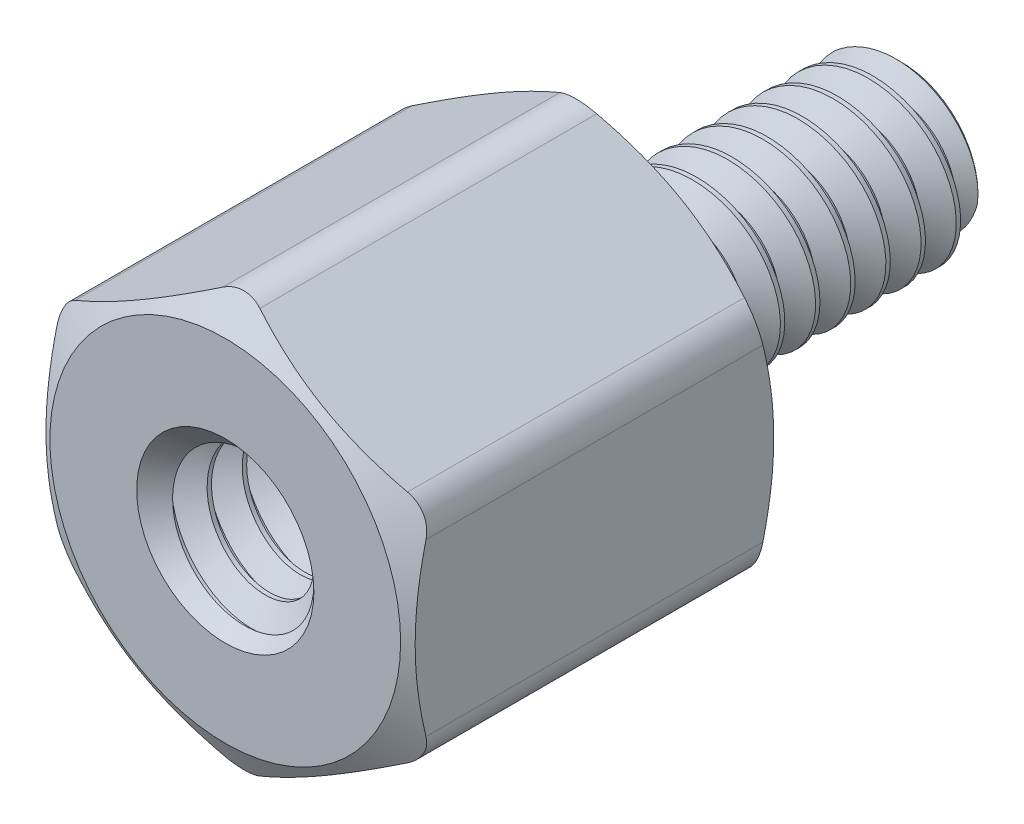
SolidWorks part; units mm, degrees
ref_plane "Front Plane" through (0, 0, 0) normal (0, 0, 1) x (1, 0, 0)
ref_plane "Top Plane" through (0, 0, 0) normal (0, 1, 0) x (1, 0, 0)
ref_plane "Right Plane" through (0, 0, 0) normal (1, 0, 0) x (0, 0, -1)
sketch "Sketch1" plane through (0, 0, 0) normal (0, 0, 1) x (1, 0, 0)
  line L1 (2.3813, 1.3748) -> (0, 2.7496)
  line L2 (0, 2.7496) -> (-2.3812, 1.3748)
  line L3 (-2.3812, 1.3748) -> (-2.3812, -1.3748)
  line L4 (-2.3812, -1.3748) -> (0, -2.7496)
  line L5 (0, -2.7496) -> (2.3813, -1.3748)
  line L6 (2.3813, -1.3748) -> (2.3813, 1.3748)
  circle A0 centre (0, 0) radius 2.3812 construction
  point P10 (0, -2.3812)
  dimension "Hex Size" = 4.7625
sketch "Sketch2" plane through (0, 0, 0) normal (1, 0, 0) x (0, 0, -1)
  line L0 (3.9688, 0) -> (-4.7625, 0) construction
  line L2 (0, 1.0922) -> (0, -1.0922) construction
  line L3 (-2.3749, 1.0922) -> (-2.3749, -1.0922) construction
  line L4 (-5.1877, 1.1413) -> (-4.9609, 0.7485) construction
  line L5 (-4.9609, 0.7485) -> (-4.7342, 1.1413) construction
  line L6 (-4.7342, 1.1413) -> (-5.1877, 1.1413) construction
  line L7 (-5.1594, 1.0922) -> (-4.7625, 1.0922) construction
  line L8 (-4.9893, 0.7976) -> (-4.9326, 0.7976) construction
  line L9 (-4.9609, 0.7976) -> (-4.9609, 0.7485) construction
  line L10 (-4.9609, 1.0922) -> (-4.9609, 1.1413) construction
  line L11 (3.9404, 1.1413) -> (4.394, 1.1413) construction
  line L12 (4.394, 1.1413) -> (4.1672, 0.7485) construction
  line L13 (4.1672, 0.7485) -> (3.9404, 1.1413) construction
  line L14 (3.9688, 1.0922) -> (4.3656, 1.0922) construction
  line L15 (4.1388, 0.7976) -> (4.1955, 0.7976) construction
  line L16 (4.1672, 0.7976) -> (4.1672, 0.7485) construction
  line L17 (4.1672, 1.0922) -> (4.1672, 1.1413) construction
  line L18 (0, 2.7496) -> (-4.7625, 2.7496) construction
  point P6 (0, 0)
  point P9 (-2.3749, 0)
  dimension "Length" = 4.7625
sketch "Sketch3" plane through (0, 0, 0) normal (1, 0, 0) x (0, 0, -1)
  line L0 (-2.3749, 0) -> (3.9688, 0)
  line L1 (-2.3749, 1.0922) -> (-2.3749, -1.0922) construction
  line L2 (3.9688, 0) -> (3.9688, 0.9788)
  line L3 (3.9688, 0.9788) -> (3.8554, 1.0922)
  line L4 (3.8554, 1.0922) -> (0.6463, 1.0922)
  line L5 (0.6463, 1.0922) -> (0.4763, 0.7976)
  line L6 (-2.3749, 0) -> (-2.3749, 0.9788)
  line L7 (-2.3749, 0.9788) -> (-2.4883, 1.0922)
  line L8 (-2.4883, 1.0922) -> (-4.6491, 1.0922)
  line L9 (-4.6491, 1.0922) -> (-4.7625, 1.2056)
  line L10 (3.8554, 0) -> (3.8554, -1.0922) construction
  line L11 (-4.7625, 1.2056) -> (-4.7625, 2.3812)
  line L12 (-4.7625, 2.3812) -> (0, 2.3812)
  line L14 (0.4763, 0.7976) -> (0.1134, 0.7976)
  line L15 (0, 0.911) -> (0, 2.3812)
  arc A0 (0, 0.911) -> (0.1134, 0.7976) centre (0.1134, 0.911) ccw
  point P5 (-4.7625, -2.3812)
  point P8 (-3.6286, -1.0922)
  point P9 (2.8348, -1.0922)
  point P27 (0, 0.7976)
  dimension "D4" = 0.1134
  dimension "D2" = 0.1134
  dimension "D1" = 45
  dimension "D6" = 1.1339
  dimension "D7" = 60
  dimension "D3" = 1.1339
  dimension "D5" = 0.4762
revolve "Revolve1" add sketch "Sketch3" angle 360 about L0 region at (0, 1.1073, 0.7097)
sketch "Sketch4" plane through (0, 0, 4.7625) normal (0, 0, 1) x (1, 0, 0)
  line L0 (0, 2.3812) -> (0, 1.0922) construction
  line L1 (-2.3812, 1.3748) -> (-2.3812, -1.3748)
  line L2 (-2.3812, -1.3748) -> (0, -2.7496)
  line L3 (0, -2.7496) -> (2.3812, -1.3748)
  line L4 (2.3812, -1.3748) -> (2.3812, 1.3748)
  line L5 (2.3812, 1.3748) -> (0, 2.7496)
  line L6 (0, 2.7496) -> (-2.3812, 1.3748)
  circle A0 centre (0, 0) radius 2.3812 construction
  circle A1 centre (0, 0) radius 1.7367
  circle A2 centre (0, 0) radius 2.3812 construction
  point P16 (0, 1.7367)
extrude "Boss-Extrude1" add sketch "Sketch4" against normal up to surface (4.7625 mm away) up to face at (0, 2.3812, 0)
sketch "Sketch5" plane through (0, 0, 4.7625) normal (0, 0, 1) x (1, 0, 0)
  line L0 (-0.6265, 0.8947) -> (0.6265, -0.8947) construction
  line L1 (0, 1.0922) -> (0, -1.0922) construction
  line L3 (0, -4.9059) -> (0, 4.9059) construction
  circle A0 centre (0, 0) radius 2.2622
  point P11 (0.6265, -0.8947)
  dimension "D1" = 4.5244
  dimension "D2" = 35
extrude "Cut-Extrude1" cut sketch "Sketch5" against normal through all draft 60 flip side to cut
sketch "Sketch6" plane through (0, 0, 0) normal (0, 0, -1) x (-1, 0, 0)
  circle A0 centre (0, 0) radius 2.2622
  circle A1 centre (0, 0) radius 2.2622 construction
extrude "Cut-Extrude2" cut sketch "Sketch6" against normal through all draft 60 flip side to cut
fillet "Fillet1" radius 0.4763 6 edges at (0, 2.7496, 2.3813) (-2.3812, -1.3748, 2.3813) (0, -2.7496, 2.3813) (2.3812, -1.3748, 2.3813) (2.3812, 1.3748, 2.3813) (-2.3812, 1.3748, 2.3813)
sketch "Drawing1" plane through (0, 0, 0) normal (1, 0, 0) x (0, 0, -1)
  line L0 (-4.7625, 1.0922) -> (-2.3749, 1.0922) construction
  line L1 (-2.3749, 1.0922) -> (-2.3749, -1.0922) construction
  line L2 (-2.3749, -1.0922) -> (-4.7625, -1.0922) construction
sketch "Sketch7" plane through (0, 0, 0) normal (-1, 0, 0) x (0, 0, 1)
  line L0 (-4.1388, 0.7976) -> (-4.1955, 0.7976)
  line L1 (-4.1955, 0.7976) -> (-4.3798, 1.1168)
  line L2 (-4.394, 1.1413) -> (-4.1672, 0.7485) construction
  line L3 (-4.3798, 1.1168) -> (-3.9546, 1.1168)
  line L4 (-4.1672, 0.7485) -> (-3.9404, 1.1413) construction
  line L5 (-3.9546, 1.1168) -> (-4.1388, 0.7976)
  line L6 (-4.1672, 1.0922) -> (-4.1672, 1.1413) construction
  point P12 (-4.1672, 1.1168)
sketch "Sketch8" plane through (0, 0, -3.9688) normal (0, 0, -1) x (-1, 0, 0)
  circle A0 centre (0, 0) radius 1.0922
curve "Helix/Spiral1" pitch 0.4536 height 3.8497 radius 1.0922 centre (0, 0, -3.9688) axis (0, 0, 1) start towards (0, 1, 0)
sweep "Cut-Sweep1" cut profiles "Sketch7" path "Helix/Spiral1" align with end faces yes
sketch "Sketch9" plane through (0, 0, 2.3749) normal (0, 0, 1) x (1, 0, 0)
  circle A0 centre (0, 0) radius 1.2056
extrude "Boss-Extrude2" add sketch "Sketch9" along normal up to surface (2.3876 mm away) up to face at (0, 1.2056, 4.7625)
sketch "Sketch10" plane through (0, 0, 0) normal (1, 0, 0) x (0, 0, -1)
  line L0 (3.9688, 0) -> (-4.7625, 0) construction
  line L1 (-2.3749, 1.0922) -> (-4.7625, 1.0922)
  line L2 (-2.3749, 1.0922) -> (-2.3749, 0)
  line L3 (-2.3749, 0) -> (-4.7625, 0)
  line L4 (-4.7625, 1.0922) -> (-4.7625, 0)
revolve "Revolve2" add sketch "Sketch10" angle 360 about L0
sketch "Sketch11" plane through (0, 0, 4.7625) normal (0, 0, 1) x (1, 0, 0)
  circle A0 centre (0, 0) radius 1.0922
  circle A1 centre (0, 0) radius 1.0922 construction
sketch "Sketch12" plane through (0, 0, 0) normal (1, 0, 0) x (0, 0, -1)
  line L0 (-4.9893, 0.7976) -> (-4.9326, 0.7976)
  line L1 (-4.9326, 0.7976) -> (-4.7483, 1.1168)
  line L2 (-4.9609, 0.7485) -> (-4.7342, 1.1413) construction
  line L3 (-4.7483, 1.1168) -> (-5.1735, 1.1168)
  line L4 (-5.1877, 1.1413) -> (-4.9609, 0.7485) construction
  line L5 (-5.1735, 1.1168) -> (-4.9893, 0.7976)
  line L6 (-4.9609, 1.0922) -> (-4.9609, 1.1413) construction
  point P12 (-4.9609, 1.1168)
curve "Helix/Spiral2" pitch 0.4536 height 2.8412 radius 1.0922 centre (0, 0, 4.7625) axis (0, 0, -1) start towards (0, 1, 0)
sweep "Cut-Sweep2" cut profiles "Sketch12" path "Helix/Spiral2" align with end faces yes
combine bodies "Combine1" operation type subtract main body 113 bodies to subtract 114
sketch "Sketch13" plane through (0, 0, 4.7625) normal (0, 0, 1) x (1, 0, 0)
  circle A0 centre (0, 0) radius 1.143
  dimension "D1" = 0.0508
extrude "Cut-Extrude3" cut sketch "Sketch13" against normal through all draft 45
equation "\"Thread Pitch (B)/8@Sketch2\"=\"Thread Pitch (B)@Sketch2\"/8"
equation "\"Thread Pitch (A)/8@Sketch2\"=\"Thread Pitch (A)@Sketch2\"/8"
equation "\"D1@Sketch5\" = \"Hex Size@Sketch1\" * .95"
equation "\"D1@Fillet1\" = \"Hex Size@Sketch1\" * .1"
equation "\"D2@Sketch3\" = \"Thread Pitch (A)@Sketch2\" * .25"
equation "\"D4@Sketch3\" = \"D2@Sketch3\""
equation "\"D6@Sketch3\" = \"Thread Pitch (A)@Sketch2\" * 2.5"
equation "\"D3@Helix/Spiral1\" = \"Thread Length (A)@Sketch2\" - \"D5@Sketch3\" * .25"
equation "\"D4@Helix/Spiral1\" = \"Thread Pitch (A)@Sketch2\""
equation "\"D3@Sketch3\" = \"Thread Pitch (B)@Sketch2\" * 2.5"
equation "\"D5@Sketch3\" = \"Thread Length (A)@Sketch2\" * .12"
equation "\"D3@Helix/Spiral2\" = \"Minimum Thread Length (B)@Sketch2\" + \"Thread Pitch (B)@Sketch2\""
equation "\"D4@Helix/Spiral2\" = \"Thread Pitch (B)@Sketch2\""
